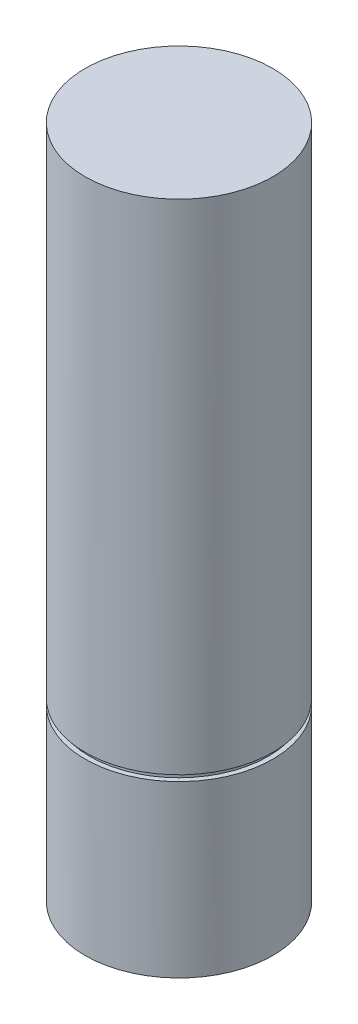
SolidWorks part; units mm, degrees
ref_plane "Front Plane" through (0, 0, 0) normal (0, 0, 1) x (1, 0, 0)
ref_plane "Top Plane" through (0, 0, 0) normal (0, 1, 0) x (1, 0, 0)
ref_plane "Right Plane" through (0, 0, 0) normal (1, 0, 0) x (0, 0, -1)
sketch "Sketch1" plane through (0, 0, 0) normal (0, 1, 0) x (1, 0, 0)
  circle A0 centre (0, 0) radius 16
  dimension "D1" = 32
extrude "Boss-Extrude1" add sketch "Sketch1" along normal blind 115
sketch "Sketch2" plane through (0, 0, 0) normal (0, -1, 0) x (1, 0, 0)
  circle A1 centre (0, 0) radius 15.2
  circle A2 centre (0, 0) radius 16 construction
  circle A3 centre (0, 0) radius 16
  circle M1 centre (0, 0) radius 16
  dimension "D1" = 0.8
extrude "Cut-Extrude2" cut sketch "Sketch2" along normal blind 1 from offset 30 contours A1 M1 region at (-15.5475, 0, 0) offset against normal yes
